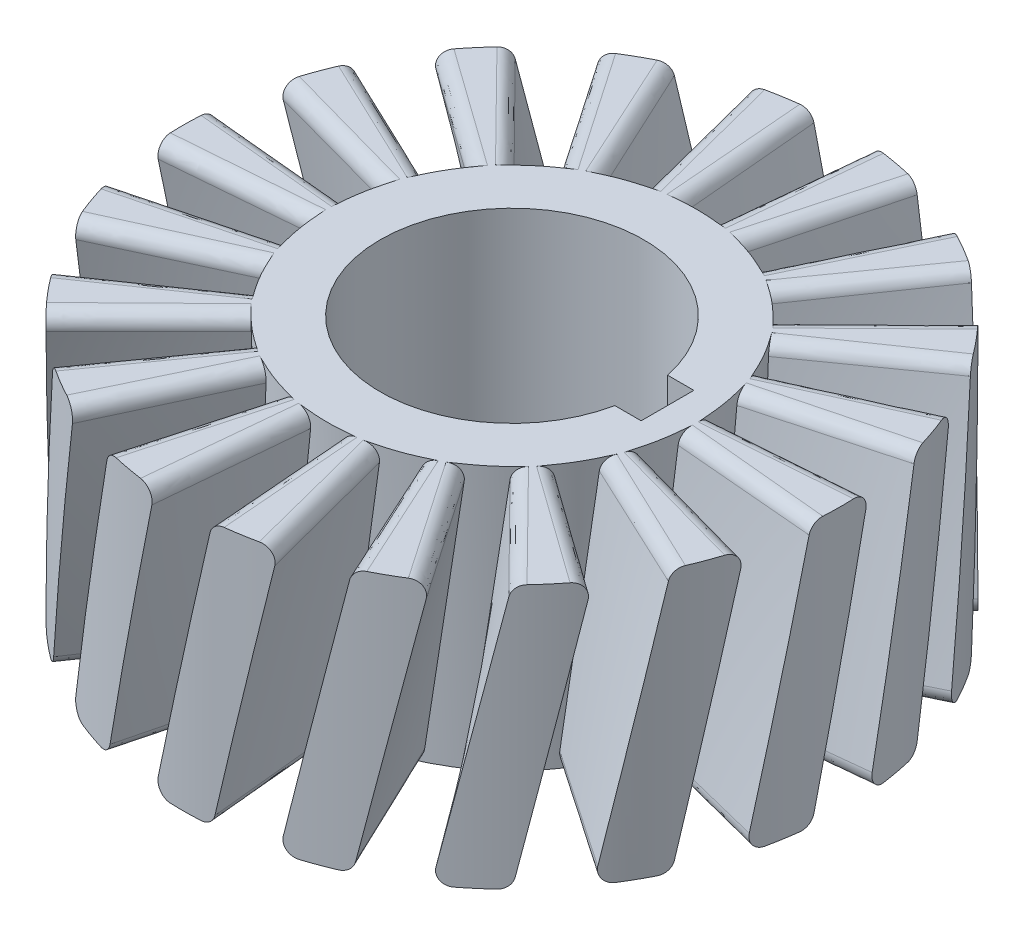
SolidWorks part; units mm, degrees
material "1023 Carbon Steel Sheet (SS)"
ref_plane "Front Plane" through (0, 0, 0) normal (0, 0, 1) x (1, 0, 0)
ref_plane "Top Plane" through (0, 0, 0) normal (0, 1, 0) x (1, 0, 0)
ref_plane "Right Plane" through (0, 0, 0) normal (1, 0, 0) x (0, 0, -1)
sketch "Sketch1" plane through (0, 0, 0) normal (0, 1, 0) x (1, 0, 0)
  circle A0 centre (0, 0) radius 37.5
  dimension "D1" = 75
extrude "Boss-Extrude1" add sketch "Sketch1" along normal blind 30
sketch "Sketch2" plane through (0, 30, 0) normal (0, 1, 0) x (1, 0, 0)
  circle A0 centre (0, 0) radius 15
  dimension "D1" = 30
extrude "Cut-Extrude1" cut sketch "Sketch2" against normal through all
ref_axis "Axis1" through (0, -0.7, 0) along (0, 1, 0)
sketch "Sketch4" plane through (0, 0, 0) normal (0, 1, 0) x (1, 0, 0)
  line L0 (0, 0) -> (37.5, 0) construction
  line L1 (0, 0) -> (37.3573, 3.2683) construction
  line L2 (0, 0) -> (37.3573, -3.2683) construction
  line L3 (20.9201, 1.8303) -> (38.3535, 3.3555)
  line L4 (20.9201, -1.8303) -> (38.3535, -3.3555)
  circle A0 centre (0, 0) radius 37.5 construction
  arc A1 (20.9201, 1.8303) -> (20.9201, -1.8303) centre (0, 0) cw
  arc A2 (38.3535, 3.3555) -> (38.3535, -3.3555) centre (0, 0) cw
  circle A3 centre (0, 0) radius 15 construction
  circle A5 centre (0, 0) radius 37.5 construction
  dimension "D1" = 10
  dimension "D2" = 6
  dimension "D3" = 1
sketch "Sketch7" plane through (0, 30, 0) normal (0, 1, 0) x (1, 0, 0)
  line L0 (0, 0) -> (36.9303, 6.5118) construction
  line L1 (0, 0) -> (37.3573, 3.2683) construction
  line L2 (0, 0) -> (36.2222, 9.7057) construction
  line L3 (0, 0) -> (37.5, 0) construction
  line L4 (20.2844, 5.4352) -> (37.1881, 9.9645)
  line L5 (20.9201, 1.8303) -> (38.3535, 3.3555)
  circle A0 centre (0, 0) radius 37.5 construction
  arc A1 (20.2844, 5.4352) -> (20.9201, 1.8303) centre (0, 0) cw
  arc A2 (37.1881, 9.9645) -> (38.3535, 3.3555) centre (0, 0) cw
  arc A3 (38.3535, -3.3555) -> (38.3535, 3.3555) centre (0, 0) ccw construction
  arc A4 (20.9201, -1.8303) -> (20.9201, 1.8303) centre (0, 0) ccw construction
  dimension "D1" = 10
  dimension "D2" = 10
loft "Cut-Loft1" cut profiles "Sketch4", "Sketch7" connector at (38.3535, 0, -3.3555) connector at (37.1881, 30, -9.9645)
fillet "Fillet2" radius 1.5 4 edges at (29.1387, 0, -2.5493)
pattern_circular "CirPattern3" count 18 over 360 about axis through (0, -0.7, 0) along (0, 1, 0) of "Cut-Loft1", "Fillet2"
sketch "Sketch8" plane through (0, 0, 0) normal (0, 1, 0) x (1, 0, 0)
  line L0 (26.3356, 0) -> (18.0347, 0) construction
  line L1 (14.6969, 3) -> (17.6969, 3)
  line L2 (17.6969, 3) -> (17.6969, -3)
  line L3 (17.6969, -3) -> (14.6969, -3)
  arc A0 (14.6969, 3) -> (14.6969, -3) centre (0, 0) cw
  circle A1 centre (0, 0) radius 15 construction
  dimension "D1" = 3
  dimension "D2" = 6
extrude "Cut-Extrude2" cut sketch "Sketch8" along normal through all
equation "\"Vane_opening\"= 10"
equation "\"D1@Sketch4\"=\"Vane_opening\""
equation "\"D1@Sketch7\"=\"Vane_opening\""
equation "\"Vane_spacing\"= 180 / \"Vane_opening\""
